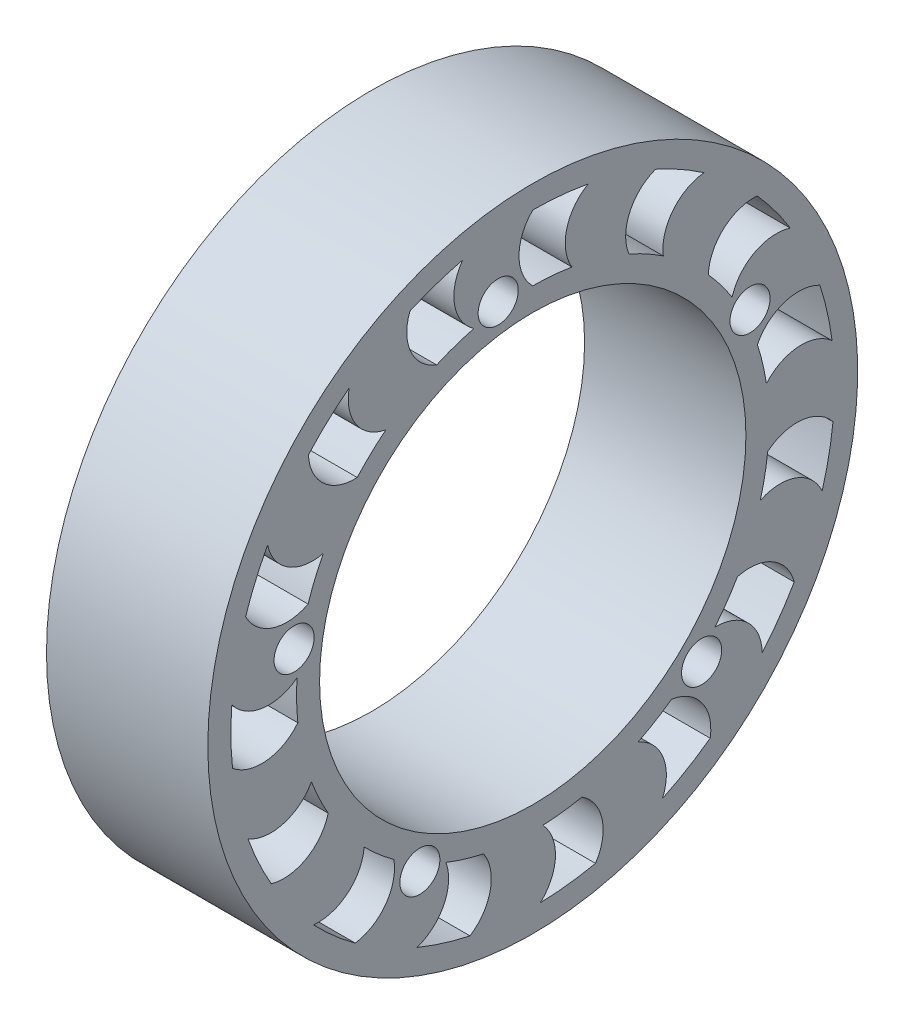
SolidWorks part; units mm, degrees
ref_plane "Front Plane" through (0, 0, 0) normal (0, 0, 1) x (1, 0, 0)
ref_plane "Top Plane" through (0, 0, 0) normal (0, 1, 0) x (1, 0, 0)
ref_plane "Right Plane" through (0, 0, 0) normal (1, 0, 0) x (0, 0, -1)
sketch "Sketch1" plane through (0, 0, 0) normal (0, 1, 0) x (1, 0, 0)
  line L0 (-17.5, 65.5) -> (17.5, 65.5)
  line L4 (17.5, 70.5) -> (-17.5, 70.5)
  line L5 (-17.5, 70.5) -> (-17.5, 65.5)
  line L6 (-1000, 0) -> (49000, 0) construction
  line L7 (17.5, 70.5) -> (17.5, 65.5)
  point P3 (0, 65.5)
  dimension "D1" = 35
  dimension "D2" = 5
  dimension "D4" = 141
revolve "Body" add sketch "Sketch1" angle 360 about L6
sketch "Sketch7" plane through (17.5, 0, 0) normal (-1, 0, 0) x (0, 0, 1)
  arc A1 (0, 65.5) -> (0, 51.25) centre (-7.0167, 58.375) cw
  circle A82 centre (0, 0) radius 46.25
  circle A83 centre (0, 0) radius 65.5 construction
  arc A84 (0, 65.5) -> (-12, 64.3914) centre (0, 0) ccw
  arc A85 (0, 51.25) -> (-8.5, 50.5402) centre (0, 0) ccw
  arc A88 (-12, 64.3914) -> (-8.5, 50.5402) centre (-17.0349, 55.7514) cw
  arc A89 (26.6413, 59.8372) -> (20.8453, 46.8192) centre (17.3332, 56.1822) cw
  circle A90 centre (0, 0) radius 51.25 construction
  arc A91 (26.6413, 59.8372) -> (15.2278, 63.7053) centre (0, 0) ccw
  arc A92 (20.8453, 46.8192) -> (12.7914, 49.628) centre (0, 0) ccw
  arc A93 (15.2278, 63.7053) -> (12.7914, 49.628) centre (7.114, 57.8601) cw
  arc A94 (48.676, 43.8281) -> (38.0862, 34.2929) centre (38.686, 44.2749) cw
  arc A95 (48.676, 43.8281) -> (39.8226, 52.004) centre (0, 0) ccw
  arc A96 (38.0862, 34.2929) -> (31.8711, 40.1347) centre (0, 0) ccw
  arc A97 (39.8226, 52.004) -> (31.8711, 40.1347) centre (30.0328, 49.9643) cw
  arc A98 (62.2942, 20.2406) -> (48.7416, 15.8371) centre (53.3496, 24.7122) cw
  arc A99 (62.2942, 20.2406) -> (57.5316, 31.3107) centre (0, 0) ccw
  arc A100 (48.7416, 15.8371) -> (45.4399, 23.7018) centre (0, 0) ccw
  arc A101 (57.5316, 31.3107) -> (45.4399, 23.7018) centre (47.7586, 33.4292) cw
  arc A102 (65.1412, -6.8466) -> (50.9692, -5.3571) centre (58.7887, 0.8764) cw
  arc A103 (65.1412, -6.8466) -> (65.293, 5.2035) centre (0, 0) ccw
  arc A104 (50.9692, -5.3571) -> (51.1518, 3.1705) centre (0, 0) ccw
  arc A105 (65.293, 5.2035) -> (51.1518, 3.1705) centre (57.2266, 11.1139) cw
  arc A106 (56.7247, -32.75) -> (44.3838, -25.625) centre (54.0626, -23.1108) cw
  arc A107 (56.7247, -32.75) -> (61.7646, -21.8034) centre (0, 0) ccw
  arc A108 (44.3838, -25.625) -> (48.0191, -17.9089) centre (0, 0) ccw
  arc A109 (61.7646, -21.8034) -> (48.0191, -17.9089) centre (56.7995, -13.123) cw
  arc A110 (38.4999, -52.9906) -> (30.124, -41.4621) centre (39.9886, -43.102) cw
  arc A111 (38.4999, -52.9906) -> (47.5565, -45.0403) centre (0, 0) ccw
  arc A112 (30.124, -41.4621) -> (36.5834, -35.8917) centre (0, 0) ccw
  arc A113 (47.5565, -45.0403) -> (36.5834, -35.8917) centre (46.5513, -35.0909) cw
  arc A114 (13.6182, -64.0687) -> (10.6555, -50.1301) centre (19.0002, -55.6405) cw
  arc A115 (13.6182, -64.0687) -> (25.1255, -60.4893) centre (0, 0) ccw
  arc A116 (10.6555, -50.1301) -> (18.8222, -47.6685) centre (0, 0) ccw
  arc A117 (25.1255, -60.4893) -> (18.8222, -47.6685) centre (28.254, -50.9913) cw
  arc A118 (-13.6182, -64.0687) -> (-10.6555, -50.1301) centre (-5.2735, -58.5582) cw
  arc A119 (-13.6182, -64.0687) -> (-1.6499, -65.4792) centre (0, 0) ccw
  arc A120 (-10.6555, -50.1301) -> (-2.1936, -51.203) centre (0, 0) ccw
  arc A121 (-1.6499, -65.4792) -> (-2.1936, -51.203) centre (5.0713, -58.0748) cw
  arc A122 (-38.4999, -52.9906) -> (-30.124, -41.4621) centre (-28.6353, -51.3507) cw
  arc A123 (-38.4999, -52.9906) -> (-28.1401, -59.1471) centre (0, 0) ccw
  arc A124 (-30.124, -41.4621) -> (-22.8301, -45.8841) centre (0, 0) ccw
  arc A125 (-28.1401, -59.1471) -> (-22.8301, -45.8841) centre (-18.9883, -55.1166) cw
  arc A126 (-56.7247, -32.75) -> (-44.3838, -25.625) centre (-47.0459, -35.2642) cw
  arc A127 (-56.7247, -32.75) -> (-49.7646, -42.588) centre (0, 0) ccw
  arc A128 (-44.3838, -25.625) -> (-39.5191, -32.6313) centre (0, 0) ccw
  arc A129 (-49.7646, -42.588) -> (-39.5191, -32.6313) centre (-39.7647, -42.6283) cw
  arc A130 (-65.1412, -6.8466) -> (-50.9692, -5.3571) centre (-57.3218, -13.0801) cw
  arc A131 (-65.1412, -6.8466) -> (-62.7843, -18.665) centre (0, 0) ccw
  arc A132 (-50.9692, -5.3571) -> (-49.3749, -13.7363) centre (0, 0) ccw
  arc A133 (-62.7843, -18.665) -> (-49.3749, -13.7363) centre (-53.6653, -22.7692) cw
  arc A134 (-62.2942, 20.2406) -> (-48.7416, 15.8371) centre (-57.6862, 11.3656) cw
  arc A135 (-62.2942, 20.2406) -> (-64.948, 8.4854) centre (0, 0) ccw
  arc A136 (-48.7416, 15.8371) -> (-50.6932, 7.5338) centre (0, 0) ccw
  arc A137 (-64.948, 8.4854) -> (-50.6932, 7.5338) centre (-58.2868, 1.027) cw
  arc A138 (-48.676, 43.8281) -> (-38.0862, 34.2929) centre (-48.0762, 33.8461) cw
  arc A139 (-48.676, 43.8281) -> (-55.8817, 34.1685) centre (0, 0) ccw
  arc A140 (-38.0862, 34.2929) -> (-43.2463, 27.5013) centre (0, 0) ccw
  arc A141 (-55.8817, 34.1685) -> (-43.2463, 27.5013) centre (-52.8299, 24.6456) cw
  arc A142 (-26.6413, 59.8372) -> (-20.8453, 46.8192) centre (-30.1533, 50.4743) cw
  arc A143 (-26.6413, 59.8372) -> (-37.1529, 53.9436) centre (0, 0) ccw
  arc A144 (-20.8453, 46.8192) -> (-28.3217, 42.7135) centre (0, 0) ccw
  arc A145 (-37.1529, 53.9436) -> (-28.3217, 42.7135) centre (-38.2382, 44.0027) cw
  point P5 (51.25, 0)
  point P99 (0, 0)
  circle M88 centre (0, 0) radius 65.5
  dimension "D1" = 92.5
  dimension "D5" = 10
  dimension "D3" = 12
  dimension "D4" = 8.5
  dimension "D6" = 10
  dimension "D2" = 5
extrude "Reinforcement" add sketch "Sketch7" along normal up to surface (35 mm away) contours A104 A107 A110 M88 region at (17.5, 63.2113, 7.4499) up to face at (-17.5, 0, 65.5)
sketch "Sketch8" plane through (-17.5, 0, 0) normal (-1, 0, 0) x (0, 0, 1)
  circle A0 centre (7.5, 52) radius 4.35
  circle A1 centre (51.7726, 8.936) radius 4.35
  circle A2 centre (24.4972, -46.4773) radius 4.35
  circle A3 centre (-36.6325, -37.6605) radius 4.35
  circle A4 centre (-47.1373, 23.2018) radius 4.35
  point P14 (0, 0)
  dimension "D1" = 8.7
  dimension "D2" = 7.5
  dimension "D3" = 52
extrude "Inserts_Holes_A" cut sketch "Sketch8" against normal blind 12.7
mirror "Mirror1" about plane through (0, 0, 0) normal (1, 0, 0) of "Inserts_Holes_A"
